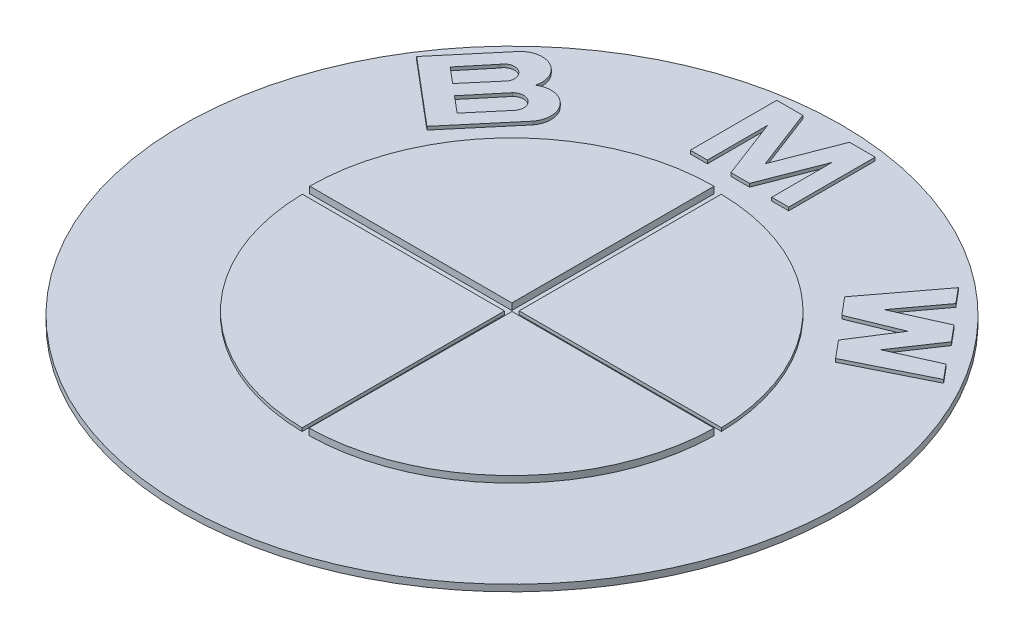
SolidWorks part; units mm, degrees
ref_plane "Front Plane" through (0, 0, 0) normal (0, 0, 1) x (1, 0, 0)
ref_plane "Top Plane" through (0, 0, 0) normal (0, 1, 0) x (1, 0, 0)
ref_plane "Right Plane" through (0, 0, 0) normal (1, 0, 0) x (0, 0, -1)
sketch "Sketch2" plane through (0, 0, 0) normal (0, 1, 0) x (1, 0, 0)
  line L2 (154.0493, -34.5217) -> (30.6053, -34.5217)
  line L3 (30.6053, -34.5217) -> (30.6053, 88.7719)
  line L4 (30.394, -162.513) -> (30.7786, -39.0255)
  line L5 (30.7786, -39.0255) -> (154.0493, -39.0255)
  line L10 (26.1861, -162.513) -> (26.1861, -39.0255)
  line L11 (26.1861, -39.0255) -> (-97.1334, -39.0255)
  line L14 (-97.1334, -34.5217) -> (26.1861, -34.5476)
  line L15 (26.1861, -34.5476) -> (26.212, 88.7719)
  line L16 (-135.0099, 68.5859) -> (-94.9902, 34.8415)
  line L17 (-94.9902, 34.8415) -> (-65.4172, 69.9141)
  line L18 (-135.0099, 68.5859) -> (-106.4178, 102.5478)
  line L19 (-119.2468, 73.2823) -> (-109.7653, 65.2571)
  line L20 (-109.7653, 65.2571) -> (-94.1581, 83.6964)
  line L21 (-119.2468, 73.2823) -> (-105.7247, 89.6634)
  line L22 (-102.7369, 59.3988) -> (-92.7437, 50.9928)
  line L23 (-92.7437, 50.9928) -> (-76.3041, 70.5363)
  line L24 (-102.7369, 59.3988) -> (-86.721, 78.6795)
  line L25 (-2.0654, 102.5478) -> (-2.0654, 155.2932)
  line L26 (-2.0654, 155.2932) -> (13.7984, 155.2932)
  line L27 (13.7984, 155.2932) -> (27.9188, 118.2487)
  line L28 (27.9188, 118.2487) -> (42.3008, 155.2932)
  line L29 (42.3008, 155.2932) -> (57.9902, 155.2932)
  line L30 (57.9902, 155.2932) -> (57.9902, 102.5478)
  line L31 (57.9902, 102.5478) -> (47.6178, 102.5478)
  line L32 (47.6178, 102.5478) -> (47.6178, 139.3422)
  line L33 (47.6178, 139.3422) -> (33.551, 103.1096)
  line L34 (33.551, 103.1096) -> (22.1661, 103.1096)
  line L35 (22.1661, 103.1096) -> (8.355, 139.3422)
  line L36 (8.355, 139.3422) -> (8.355, 102.5478)
  line L37 (8.355, 102.5478) -> (-2.0654, 102.5478)
  line L38 (122.4653, 72.188) -> (131.3393, 61.5885)
  line L39 (131.3393, 61.5885) -> (159.9333, 73.2823)
  line L40 (159.9333, 73.2823) -> (143.4178, 47.4558)
  line L41 (143.4178, 47.4558) -> (152.283, 36.8668)
  line L42 (152.283, 36.8668) -> (196.3371, 58.7057)
  line L43 (196.3371, 58.7057) -> (188.9325, 67.55)
  line L44 (188.9325, 67.55) -> (161.5118, 55.2726)
  line L45 (161.5118, 55.2726) -> (178.7954, 80.9871)
  line L46 (178.7954, 80.9871) -> (170.7102, 90.6445)
  line L47 (170.7102, 90.6445) -> (141.3693, 77.5073)
  line L48 (141.3693, 77.5073) -> (159.9333, 102.5478)
  line L49 (159.9333, 102.5478) -> (152.283, 111.6856)
  line L50 (152.283, 111.6856) -> (122.4653, 72.188)
  circle A0 centre (28.7283, -36.9991) radius 201.0315
  arc A2 (26.212, 88.7719) -> (-97.1334, -34.5217) centre (26.1861, -34.5476) ccw
  arc A4 (-97.1334, -39.0255) -> (26.1861, -162.513) centre (28.4323, -36.9503) ccw
  arc A6 (30.394, -162.513) -> (154.0493, -39.0255) centre (28.7401, -37.2015) ccw
  arc A8 (154.0493, -34.5217) -> (30.6053, 88.7719) centre (28.3815, -36.8987) ccw
  arc A10 (-105.7247, 89.6634) -> (-94.1581, 83.6964) centre (-99.9414, 86.6799) cw
  arc A11 (-86.721, 78.6795) -> (-76.3041, 70.5363) centre (-81.9011, 74.1109) cw
  arc A12 (-106.4178, 102.5478) -> (-83.6982, 89.6634) centre (-96.6358, 93.3235) cw
  arc A13 (-83.6982, 89.6634) -> (-65.4172, 69.9141) centre (-76.3153, 78.1618) cw
  point P3 (0, 0)
extrude "Boss-Extrude7" add sketch "Sketch2" along normal blind 4 contours A0 L50 L49 L48 L47 L46 L45 L44 L43 L42 L41 L40 L39 L38 L36 L37 L25 L26 L27 L28 L29 L30 L31 L32 L33 L34 L35 A2 L15 L14 A4 L11 L10 A6 L4 L5 A8 L2 L3 A12 A13 L17 L16 L18 | A11 L24 L22 L23 | A10 L21 L19 L20 region at (-105.4944, 0, -80.0519) region at (-88.1014, 0, -66.7194) region at (30.5212, 0, 49.4198)
extrude "Boss-Extrude10" add sketch "Sketch2<12>" along normal blind 6 contours A13 A12 L18 L16 L17 L21 A10 L20 L19 L24 A11 L23 L22 | L37 L36 L35 L34 L33 L32 L31 L30 L29 L28 L27 L26 L25 | L49 L50 L38 L39 L40 L41 L42 L43 L44 L45 L46 L47 L48 | L2 A8 L3 | L11 A4 L10 region at (82.6966, 0, -17.5149) region at (-25.8796, 0, 91.1523) region at (-97.206, 0, -72.724) region at (-1.2661, 0, -128.9205) region at (138.2133, 0, -91.3033)
sketch "Sketch2<12>" plane through (0, 0, 0) normal (0, 1, 0) x (1, 0, 0) same geometry as "Sketch2"
extrude "Boss-Extrude11" add sketch "Sketch2<13>" along normal blind 8 contours L15 A2 L14 | L4 A6 L5 region at (82.7494, 0, 91.2378) region at (-26.1413, 0, -17.8018)
sketch "Sketch2<13>" plane through (0, 0, 0) normal (0, 1, 0) x (1, 0, 0) same geometry as "Sketch2"
